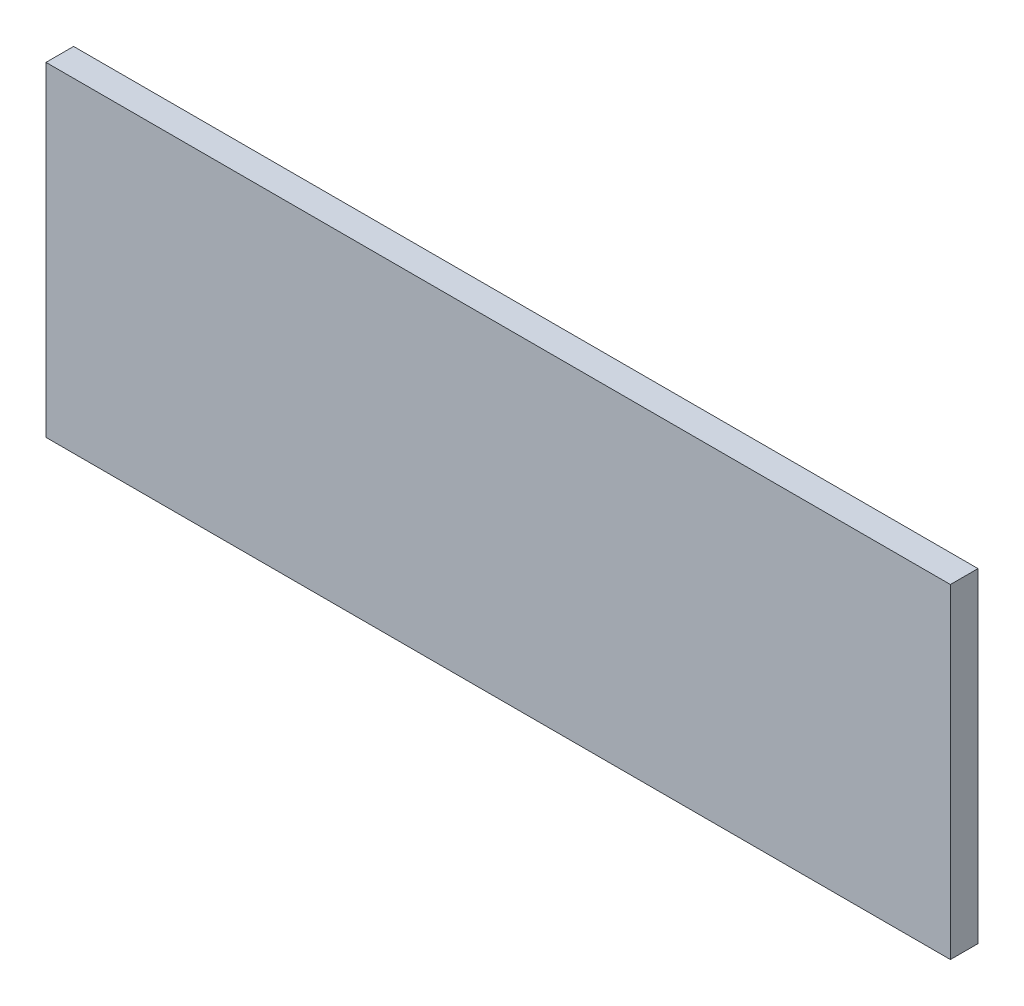
SolidWorks part; units mm, degrees
ref_plane "正面" through (0, 0, 0) normal (0, 0, 1) x (1, 0, 0)
ref_plane "平面" through (0, 0, 0) normal (0, 1, 0) x (1, 0, 0)
ref_plane "右側面" through (0, 0, 0) normal (1, 0, 0) x (0, 0, -1)
sketch "ｽｹｯﾁ1" plane through (0, 0, 0) normal (0, 0, 1) x (1, 0, 0)
  line L1 (-69.2801, 161.5071) -> (356.7199, 161.5071)
  line L2 (-69.2801, 161.5071) -> (-69.2801, 8.5071)
  line L3 (-69.2801, 8.5071) -> (356.7199, 8.5071)
  line L4 (356.7199, 161.5071) -> (356.7199, 8.5071)
  dimension "D1" = 426
  dimension "D3" = 153
extrude "ﾎﾞｽ - 押し出し1" add sketch "ｽｹｯﾁ1" along normal blind 13
